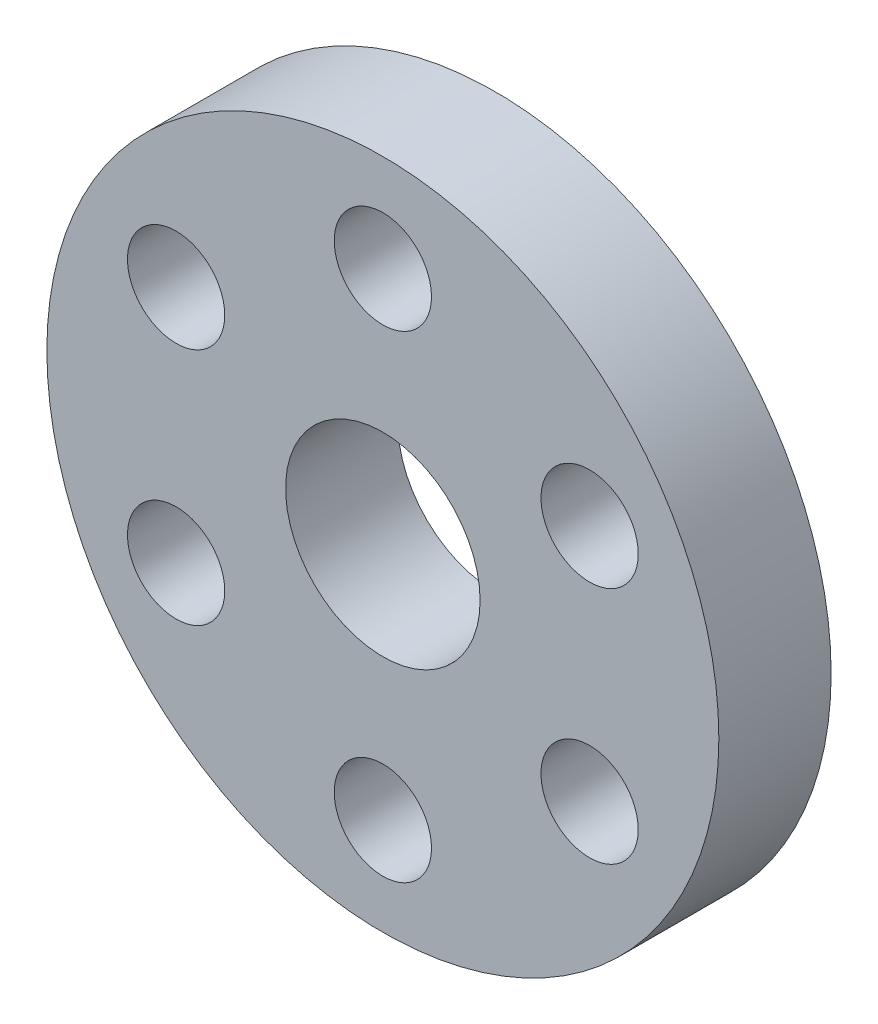
SolidWorks part; units mm, degrees
ref_plane "Front Plane" through (0, 0, 0) normal (0, 0, 1) x (1, 0, 0)
ref_plane "Top Plane" through (0, 0, 0) normal (0, 1, 0) x (1, 0, 0)
ref_plane "Right Plane" through (0, 0, 0) normal (1, 0, 0) x (0, 0, -1)
sketch "Sketch1" plane through (0, 0, 0) normal (0, 0, 1) x (1, 0, 0)
  circle A0 centre (0, 0) radius 19
  circle A1 centre (0, 0) radius 5.5
  dimension "D1" = 38
  dimension "D2" = 11
extrude "1/4" add sketch "Sketch1" along normal blind 6.35
sketch "Sketch2" plane through (0, 0, 0) normal (0, 0, 1) x (1, 0, 0)
  circle A0 centre (0, 0) radius 13.5 construction
  circle A1 centre (0, 13.5) radius 2.75
  circle A2 centre (11.6913, 6.75) radius 2.75
  circle A3 centre (11.6913, -6.75) radius 2.75
  circle A4 centre (0, -13.5) radius 2.75
  circle A5 centre (-11.6913, -6.75) radius 2.75
  circle A6 centre (-11.6913, 6.75) radius 2.75
  point P17 (0, 0)
  dimension "D1" = 27
  dimension "D2" = 5.5
  dimension "D3" = 6
extrude "M5_through" cut sketch "Sketch2" along normal up to surface (6.35 mm away) up to face at (19, 0, 6.35)
